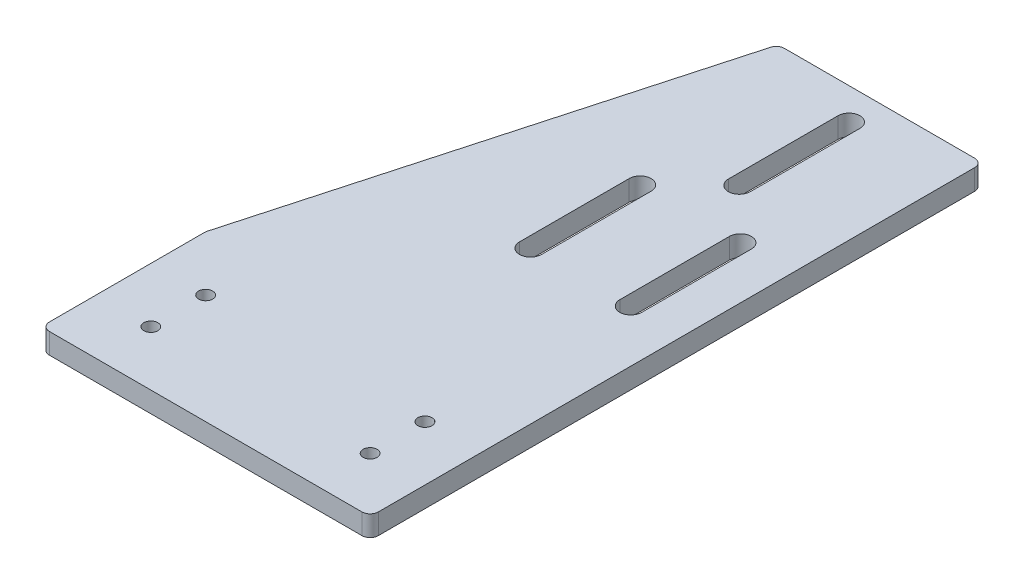
SolidWorks part; units mm, degrees
material "6061-T6 (SS)"
ref_plane "Front Plane" through (0, 0, 0) normal (0, 0, 1) x (1, 0, 0)
ref_plane "Top Plane" through (0, 0, 0) normal (0, 1, 0) x (1, 0, 0)
ref_plane "Right Plane" through (0, 0, 0) normal (1, 0, 0) x (0, 0, -1)
sketch "Sketch1" plane through (0, 0, 0) normal (0, 1, 0) x (1, 0, 0)
  line L0 (0, 0) -> (-23.1679, -73.5829) construction
  line L1 (-23.1679, -73.5829) -> (23.2637, -73.5829) construction
  line L2 (23.2637, -73.5829) -> (0, 0) construction
  line L3 (-40.0054, -96.3532) -> (36.1942, -96.0984) construction
  circle A0 centre (0, 0) radius 5.08
  circle A1 centre (-23.1679, -73.5829) radius 5.08
  circle A2 centre (23.2637, -73.5829) radius 5.08
  dimension "D6" = 10.16
  dimension "D1" = 35.022
  dimension "D2" = 77.144
  dimension "D3" = 77.1728
  dimension "D4" = 46.4316
  dimension "D5" = 72.455
  dimension "D7" = 76.2
  dimension "D8" = 72.523
sketch "Sketch3" plane through (0, 0, 0) normal (0, 1, 0) x (1, 0, 0)
  line L0 (-23.1679, -83.7429) -> (-23.1679, -32.9429) construction
  line L1 (-47.3937, 55.245) -> (47.3937, 55.245)
  line L2 (-47.3937, 55.245) -> (-47.3937, -228.6) construction
  line L3 (-105.0063, -228.6) -> (47.3937, -228.6)
  line L4 (47.3937, 55.245) -> (47.3937, -228.6)
  line L5 (-28.2479, -83.7429) -> (-28.2479, -32.9429)
  line L6 (-18.0879, -83.7429) -> (-18.0879, -32.9429)
  line L7 (23.2637, -83.7429) -> (23.2637, -32.9429) construction
  line L8 (18.1837, -83.7429) -> (18.1837, -32.9429)
  line L9 (28.3437, -83.7429) -> (28.3437, -32.9429)
  line L10 (0, -10.16) -> (0, 40.64) construction
  line L13 (-5.08, -10.16) -> (-5.08, 40.64)
  line L14 (5.08, -10.16) -> (5.08, 40.64)
  line L15 (-23.1679, -73.5829) -> (23.2637, -73.5829) construction
  line L16 (-47.3937, 55.245) -> (-105.0063, -152.4)
  line L17 (-105.0063, -152.4) -> (-105.0063, -228.6)
  line L18 (-105.0063, -165.1) -> (47.3937, -165.1) construction
  arc A0 (-28.2479, -83.7429) -> (-18.0879, -83.7429) centre (-23.1679, -83.7429) ccw
  arc A1 (-18.0879, -32.9429) -> (-28.2479, -32.9429) centre (-23.1679, -32.9429) ccw
  arc A2 (18.1837, -83.7429) -> (28.3437, -83.7429) centre (23.2637, -83.7429) ccw
  arc A3 (28.3437, -32.9429) -> (18.1837, -32.9429) centre (23.2637, -32.9429) ccw
  arc A6 (-5.08, -10.16) -> (5.08, -10.16) centre (0, -10.16) ccw
  arc A7 (5.08, 40.64) -> (-5.08, 40.64) centre (0, 40.64) ccw
  circle A8 centre (21.9937, -203.2) radius 3.2512
  circle A9 centre (21.9937, -177.8) radius 3.2512
  circle A10 centre (-79.6063, -177.8) radius 3.2512
  circle A11 centre (-79.6063, -203.2) radius 3.2512
  point P6 (-23.1679, -58.3429)
  point P14 (23.2637, -58.3429)
  point P22 (0, 15.24)
  point P31 (0, 55.245)
  point P32 (0, 45.72)
  dimension "D9" = 6.5024
  dimension "D1" = 10.16
  dimension "D2" = 10.16
  dimension "D3" = 10.16
  dimension "D4" = 50.8
  dimension "D5" = 9.525
  dimension "D7" = 19.05
  dimension "D10" = 25.4
  dimension "D11" = 101.6
  dimension "D12" = 25.4
  dimension "D13" = 25.4
  dimension "D14" = 177.8
  dimension "D6" = 25.4
  dimension "D8" = 25.4
  dimension "D15" = 46.9216
  dimension "D16" = 12.7
sketch "Sketch4" plane through (0, 0, 0) normal (0, 1, 0) x (1, 0, 0)
  line L0 (18.1837, -83.7429) -> (18.1837, -32.9429) construction
  line L1 (28.3437, -83.7429) -> (28.3437, -32.9429) construction
  line L2 (-5.08, -10.16) -> (-5.08, 40.64) construction
  line L3 (5.08, -10.16) -> (5.08, 40.64) construction
  line L4 (-28.2479, -83.7429) -> (-28.2479, -32.9429) construction
  line L5 (-18.0879, -83.7429) -> (-18.0879, -32.9429) construction
  line L6 (-47.3937, 55.245) -> (-105.0063, -152.4) construction
  line L7 (-105.0063, -152.4) -> (-105.0063, -228.6) construction
  line L8 (-105.0063, -228.6) -> (47.3937, -228.6) construction
  line L9 (47.3937, 55.245) -> (47.3937, -228.6) construction
  line L10 (-47.3937, 55.245) -> (47.3937, 55.245) construction
  line L11 (18.1837, -83.7429) -> (18.1837, -32.9429)
  line L12 (28.3437, -83.7429) -> (28.3437, -32.9429)
  line L13 (-5.08, -10.16) -> (-5.08, 40.64)
  line L14 (5.08, -10.16) -> (5.08, 40.64)
  line L15 (-28.2479, -83.7429) -> (-28.2479, -32.9429)
  line L16 (-18.0879, -83.7429) -> (-18.0879, -32.9429)
  line L17 (-48.1682, 52.4536) -> (-104.8676, -151.9001)
  line L18 (-105.0063, -152.9188) -> (-105.0063, -224.79)
  line L19 (-101.1963, -228.6) -> (43.5837, -228.6)
  line L20 (47.3937, 51.435) -> (47.3937, -224.79)
  line L21 (-44.4969, 55.245) -> (43.5837, 55.245)
  circle A0 centre (21.9937, -203.2) radius 3.2512 construction
  circle A1 centre (21.9937, -177.8) radius 3.2512 construction
  circle A2 centre (-79.6063, -203.2) radius 3.2512 construction
  circle A3 centre (-79.6063, -177.8) radius 3.2512 construction
  arc A4 (28.3437, -32.9429) -> (18.1837, -32.9429) centre (23.2637, -32.9429) ccw construction
  arc A5 (18.1837, -83.7429) -> (28.3437, -83.7429) centre (23.2637, -83.7429) ccw construction
  arc A6 (5.08, 40.64) -> (-5.08, 40.64) centre (0, 40.64) ccw construction
  arc A7 (-5.08, -10.16) -> (5.08, -10.16) centre (0, -10.16) ccw construction
  arc A8 (-18.0879, -32.9429) -> (-28.2479, -32.9429) centre (-23.1679, -32.9429) ccw construction
  arc A9 (-28.2479, -83.7429) -> (-18.0879, -83.7429) centre (-23.1679, -83.7429) ccw construction
  circle A10 centre (21.9937, -203.2) radius 3.2512
  circle A11 centre (21.9937, -177.8) radius 3.2512
  circle A12 centre (-79.6063, -203.2) radius 3.2512
  circle A13 centre (-79.6063, -177.8) radius 3.2512
  arc A14 (28.3437, -32.9429) -> (18.1837, -32.9429) centre (23.2637, -32.9429) ccw
  arc A15 (18.1837, -83.7429) -> (28.3437, -83.7429) centre (23.2637, -83.7429) ccw
  arc A16 (5.08, 40.64) -> (-5.08, 40.64) centre (0, 40.64) ccw
  arc A17 (-5.08, -10.16) -> (5.08, -10.16) centre (0, -10.16) ccw
  arc A18 (-18.0879, -32.9429) -> (-28.2479, -32.9429) centre (-23.1679, -32.9429) ccw
  arc A19 (-28.2479, -83.7429) -> (-18.0879, -83.7429) centre (-23.1679, -83.7429) ccw
  arc A20 (43.5837, -228.6) -> (47.3937, -224.79) centre (43.5837, -224.79) ccw
  arc A21 (-105.0063, -224.79) -> (-101.1963, -228.6) centre (-101.1963, -224.79) ccw
  arc A22 (-104.8676, -151.9001) -> (-105.0063, -152.9188) centre (-101.1963, -152.9188) ccw
  arc A23 (-48.1682, 52.4536) -> (-44.4969, 55.245) centre (-44.4969, 51.435) cw
  arc A24 (47.3937, 51.435) -> (43.5837, 55.245) centre (43.5837, 51.435) ccw
  dimension "D1" = 3.81
extrude "Boss-Extrude1" add sketch "Sketch4" along normal blind 9.525
sketch "Sketch9" plane through (0, 9.525, 0) normal (0, 1, 0) x (1, 0, 0)
  line L0 (-105.0063, -190.5) -> (47.3937, -190.5) construction
  line L1 (-105.0063, -152.9188) -> (-105.0063, -224.79) construction
  line L2 (47.3937, -224.79) -> (47.3937, 51.435) construction
  circle A0 centre (-79.6063, -177.8) radius 3.2512 construction
  circle A1 centre (-79.6063, -203.2) radius 3.2512 construction
  dimension "D1" = 12.7
  dimension "D2" = 12.7
sketch "Sketch10" plane through (0, 9.525, 0) normal (0, 1, 0) x (1, 0, 0)
  line L4 (35.9637, -78.74) -> (35.9637, 100.0394)
  line L5 (47.3937, -224.79) -> (47.3937, 51.435)
  line L6 (43.5837, 55.245) -> (-44.4969, 55.245)
  line L7 (-48.1682, 52.4536) -> (-104.8676, -151.9001)
  line L8 (-105.0063, -152.9188) -> (-105.0063, -224.79)
  line L9 (-101.1963, -228.6) -> (43.5837, -228.6)
  line L10 (47.3937, -224.79) -> (47.3937, 51.435)
  line L11 (43.5837, 55.245) -> (-44.4969, 55.245)
  line L12 (-48.1682, 52.4536) -> (-104.8676, -151.9001)
  line L13 (-105.0063, -152.9188) -> (-105.0063, -224.79)
  line L14 (-101.1963, -228.6) -> (43.5837, -228.6)
  line L15 (35.9637, 100.0394) -> (-6.7019, 100.0394)
  line L16 (-6.7019, 100.0394) -> (-45.8075, -78.74)
  line L17 (-45.8075, -78.74) -> (35.9637, -78.74)
  line L18 (28.3437, -83.7429) -> (28.3437, -32.9429) construction
  arc A0 (-18.0879, -32.9429) -> (-28.2479, -32.9429) centre (-23.1679, -32.9429) ccw construction
  arc A1 (5.08, 40.64) -> (-5.08, 40.64) centre (0, 40.64) ccw construction
  arc A2 (-5.08, -10.16) -> (5.08, -10.16) centre (0, -10.16) ccw construction
  arc A5 (43.5837, -228.6) -> (47.3937, -224.79) centre (43.5837, -224.79) ccw
  arc A6 (47.3937, 51.435) -> (43.5837, 55.245) centre (43.5837, 51.435) ccw
  arc A7 (-44.4969, 55.245) -> (-48.1682, 52.4536) centre (-44.4969, 51.435) ccw
  arc A8 (-104.8676, -151.9001) -> (-105.0063, -152.9188) centre (-101.1963, -152.9188) ccw
  arc A9 (-105.0063, -224.79) -> (-101.1963, -228.6) centre (-101.1963, -224.79) ccw
  arc A10 (43.5837, -228.6) -> (47.3937, -224.79) centre (43.5837, -224.79) ccw
  arc A11 (47.3937, 51.435) -> (43.5837, 55.245) centre (43.5837, 51.435) ccw
  arc A12 (-44.4969, 55.245) -> (-48.1682, 52.4536) centre (-44.4969, 51.435) ccw
  arc A13 (-104.8676, -151.9001) -> (-105.0063, -152.9188) centre (-101.1963, -152.9188) ccw
  arc A14 (-105.0063, -224.79) -> (-101.1963, -228.6) centre (-101.1963, -224.79) ccw
  dimension "D5" = 19.2398
  dimension "D6" = 68.58
  dimension "D2" = 7.62
  dimension "D3" = 78.74
  dimension "D4" = 12.3306
  dimension "D1" = 0
split line "Split Line1"
equation "\"D2@Sketch3\"=\"D1@Sketch3\""
